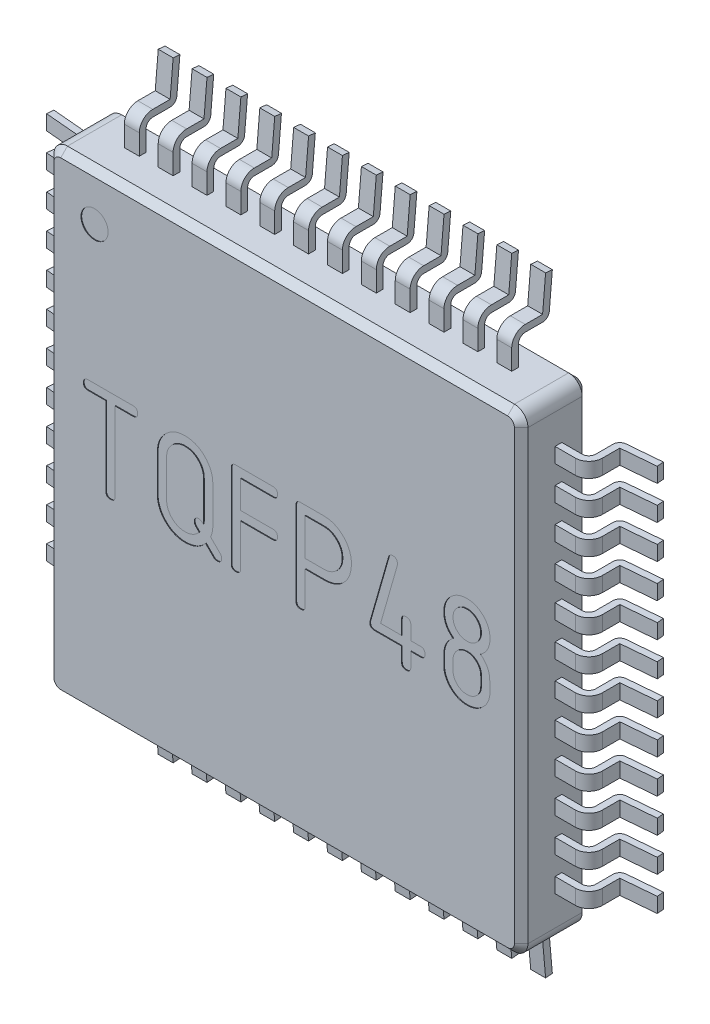
SolidWorks part; units mm, degrees
ref_plane "Спереди" through (0, 0, 0) normal (0, 0, 1) x (1, 0, 0)
ref_plane "Сверху" through (0, 0, 0) normal (0, 1, 0) x (1, 0, 0)
ref_plane "Справа" through (0, 0, 0) normal (1, 0, 0) x (0, 0, -1)
ref_axis "Ось1" through (0, 0, -0.055) along (0, 0, 1)
sketch "Эскиз1" plane through (0, 0, 0) normal (0, 0, 1) x (1, 0, 0)
  line L0 (0, 0) -> (-4.5, 0) construction
  line L1 (-3.5, -3.5) -> (3.5, -3.5)
  line L2 (-3.5, -3.5) -> (-3.5, 3.5)
  line L3 (-3.5, 3.5) -> (3.5, 3.5)
  line L4 (3.5, -3.5) -> (3.5, 3.5)
  line L5 (-3.5, -3.5) -> (3.5, 3.5) construction
  line L6 (-3.5, 3.5) -> (3.5, -3.5) construction
  line L7 (-4.5, -4.5) -> (4.5, -4.5)
  line L8 (-4.5, -4.5) -> (-4.5, 4.5)
  line L9 (-4.5, 4.5) -> (4.5, 4.5)
  line L10 (4.5, -4.5) -> (4.5, 4.5)
  line L11 (-4.5, -4.5) -> (4.5, 4.5) construction
  line L12 (-4.5, 4.5) -> (4.5, -4.5) construction
  point P0 (0, 0)
  point P6 (0, 0)
  point P13 (-3.5, 0.75)
  point P14 (-3.5, 1.25)
  point P15 (-3.5, 1.75)
  point P16 (-3.5, 2.25)
  point P17 (-3.5, -2.25)
  point P18 (-3.5, -1.75)
  point P19 (-3.5, -1.25)
  point P20 (-3.5, -0.75)
  point P21 (-3.5, 0.25)
  point P22 (-3.5, 2.75)
  point P23 (-3.5, -2.75)
  point P24 (-3.5, -0.25)
ref_plane "Плоскость1" through (0, 0, 0.1) normal (0, 0, 1) x (1, 0, 0)
ref_plane "Плоскость2" through (0, 2.75, 0) normal (0, 1, 0) x (-1, 0, 0)
sketch "Эскиз2" plane through (0, 0, 0.1) normal (0, 0, 1) x (1, 0, 0)
  line L0 (-3.5, 3.5) -> (3.5, 3.5) construction
  line L1 (-3.5, -3.5) -> (-3.5, 3.5) construction
  line L2 (-3.5, -3.5) -> (3.5, -3.5) construction
  line L3 (3.5, -3.5) -> (3.5, 3.5) construction
  line L4 (-3.3, 3.5) -> (3.3, 3.5)
  line L5 (-3.5, -3.3) -> (-3.5, 3.3)
  line L6 (-3.3, -3.5) -> (3.3, -3.5)
  line L7 (3.5, -3.3) -> (3.5, 3.3)
  arc A0 (-3.5, -3.3) -> (-3.3, -3.5) centre (-3.3, -3.3) ccw
  arc A1 (3.3, -3.5) -> (3.5, -3.3) centre (3.3, -3.3) ccw
  arc A2 (3.3, 3.5) -> (3.5, 3.3) centre (3.3, 3.3) cw
  arc A3 (-3.3, 3.5) -> (-3.5, 3.3) centre (-3.3, 3.3) ccw
  dimension "D1" = 0.2
extrude "Бобышка-Вытянуть1" add sketch "Эскиз2" along normal blind 1
chamfer "Фаска1" distance 0.1 angle 45 16 edges at (0, 3.5, 0.1) (-3.4414, 3.4414, 0.1) (3.4414, 3.4414, 0.1) (-3.5, 0, 0.1) (3.5, 0, 0.1) (-3.4414, -3.4414, 0.1) (3.4414, -3.4414, 0.1) (0, -3.5, 0.1) (0, 3.5, 1.1) (-3.4414, 3.4414, 1.1) (3.4414, 3.4414, 1.1) (-3.5, 0, 1.1) (3.5, 0, 1.1) (-3.4414, -3.4414, 1.1) (3.4414, -3.4414, 1.1) (0, -3.5, 1.1)
sketch "Эскиз3" plane through (0, 2.75, 0) normal (0, 1, 0) x (-1, 0, 0)
  line L0 (3.5, 0.5) -> (3.8, 0.5)
  line L1 (3.9, 0.4) -> (3.9, 0.1441)
  line L2 (3.9913, 0.0445) -> (4.5, 0)
  line L3 (55, 0) -> (-55, 0) construction
  line L4 (3.5, 0.6) -> (3.8, 0.6)
  line L5 (4, 0.4) -> (4, 0.1441)
  line L6 (4, 0.1441) -> (4.5087, 0.0996)
  line L7 (3.5, 0.5) -> (3.5, 0.6)
  line L8 (4.5, 0) -> (4.5087, 0.0996)
  arc A0 (3.9, 0.1441) -> (3.9913, 0.0445) centre (4, 0.1441) ccw
  arc A1 (3.8, 0.5) -> (3.9, 0.4) centre (3.8, 0.4) cw
  arc A2 (3.8, 0.6) -> (4, 0.4) centre (3.8, 0.4) cw
  arc A3 (4, 0.1441) -> (4, 0.1441) centre (4, 0.1441) ccw
  dimension "D1" = 0.1
  dimension "D2" = 0.6
  dimension "D3" = 5
  dimension "D4" = 0.5
  dimension "D5" = 0.1
extrude "Бобышка-Вытянуть2" add sketch "Эскиз3" along normal blind 0.11 and the other way blind 0.11
pattern_linear "Линейный массив1" count 12 spacing 0.5 along (0, -1, 0) of "Бобышка-Вытянуть2"
pattern_circular "Круговой массив1" count 4 over 360 about axis through (0, 0, -0.055) along (0, 0, 1) of "Бобышка-Вытянуть2", "Линейный массив1"
sketch "Эскиз4" plane through (0, 0, 1.1) normal (0, 0, 1) x (1, 0, 0)
  circle A0 centre (-2.8, 2.8) radius 0.2
  text T0 "TQFP48" font "ГОСТ тип А" height in points 6
  dimension "D1" = 0.4
  dimension "D2" = 3.1
  dimension "D3" = 0.6
extrude "Вырез-Вытянуть1" cut sketch "Эскиз4" against normal blind 0.01
